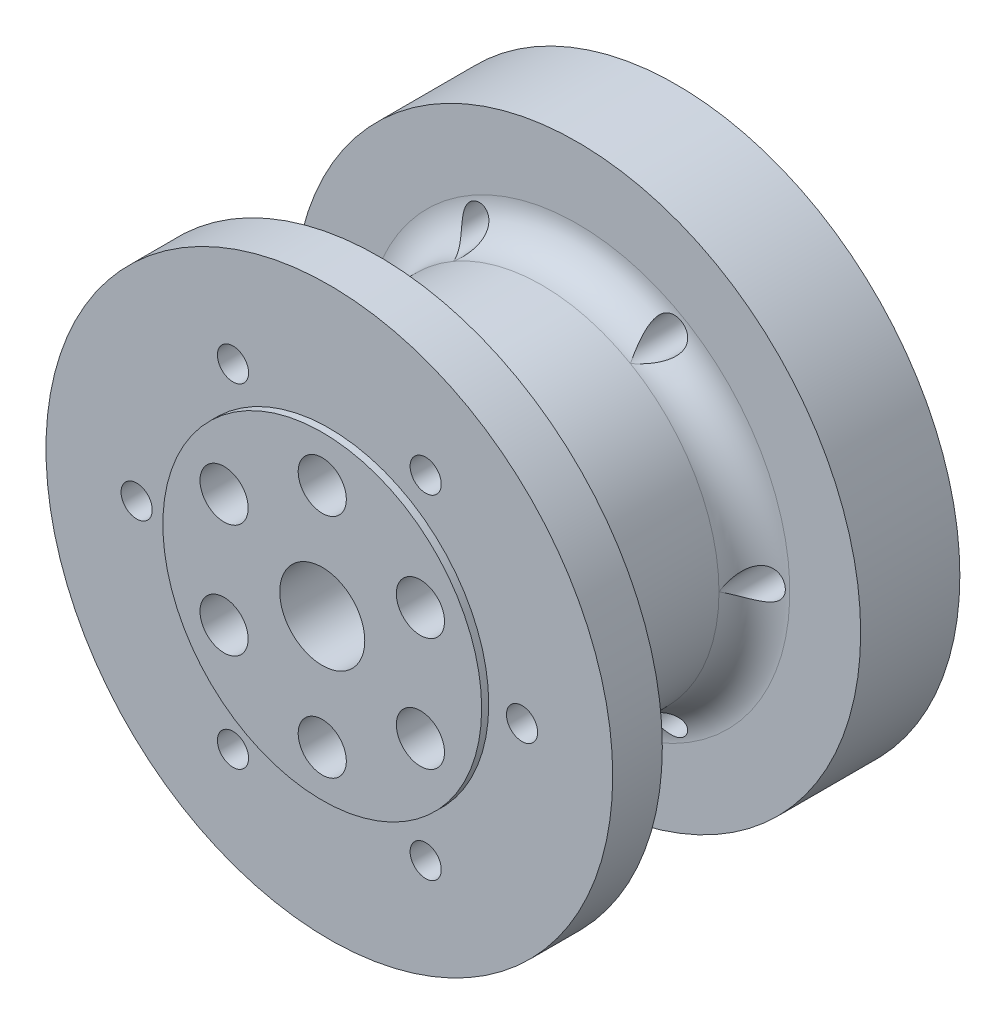
SolidWorks part; units mm, degrees
material "Nylon - impressão"
ref_plane "Plano frontal" through (0, 0, 0) normal (0, 0, 1) x (1, 0, 0)
ref_plane "Plano superior" through (0, 0, 0) normal (0, 1, 0) x (1, 0, 0)
ref_plane "Plano direito" through (0, 0, 0) normal (1, 0, 0) x (0, 0, -1)
sketch "Esboço1" plane through (0, 0, 0) normal (1, 0, 0) x (0, 0, -1)
  line L0 (1.5, 11.25) -> (1.5, 20)
  line L1 (1.5, 20) -> (5, 20)
  line L2 (5, 20) -> (5, 12.5)
  line L3 (5, 12.5) -> (19, 12.5)
  line L4 (19, 12.5) -> (19, 20)
  line L5 (19, 20) -> (27, 20)
  line L6 (27, 20) -> (27, 3)
  line L9 (27, 3) -> (0, 3)
  line L10 (0, 3) -> (0, 11.25)
  line L11 (0, 11.25) -> (1.5, 11.25)
  line L12 (0, 0) -> (24.3309, 0) construction
  line L14 (0, 11.25) -> (-3, 11.25) construction
  line L15 (0, 11.25) -> (0, 3) construction
  line L16 (0, 3) -> (-3, 3) construction
  line L17 (-3, 11.25) -> (-3, 3) construction
  dimension "D1" = 25
  dimension "D2" = 6
  dimension "D3" = 14
  dimension "D4" = 22.5
  dimension "D5" = 30
  dimension "D6" = 5
  dimension "D7" = 1.5
  dimension "D8" = 3
  dimension "D9" = 40
revolve "Revolução1" add sketch "Esboço1" angle 360 about L12
sketch "Esboço2" plane through (0, 0, -27) normal (0, 0, -1) x (-1, 0, 0)
  circle A0 centre (0, 0) radius 8 construction
  circle A1 centre (0, 8) radius 1.6
  circle A2 centre (6.9282, 4) radius 1.6
  circle A3 centre (6.9282, -4) radius 1.6
  circle A4 centre (0, -8) radius 1.6
  circle A5 centre (-6.9282, -4) radius 1.6
  circle A6 centre (-6.9282, 4) radius 1.6
  point P17 (0, 0)
  dimension "D1" = 16
  dimension "D2" = 3.2
  dimension "D3" = 6
extrude "Corte-extrusão1" cut sketch "Esboço2" against normal through all
hole_wizard "Rebaixo para SHCS M31" positions "Esboço3" profile "Esboço4" counterbore size "M3" standard "Ansi Metric" end condition through all
sketch "Esboço3" plane through (0, 0, -27) normal (0, 0, -1) x (-1, 0, 0)
  point P0 (0, 8)
  point P3 (-6.9282, 4)
  point P6 (-6.9282, -4)
  point P9 (0, -8)
  point P12 (6.9282, -4)
  point P15 (6.9282, 4)
sketch "Esboço4" plane through (0, 8, -27) normal (1, 0, 0) x (0, 1, 0)
  line L0 (0, 0) -> (0, 27)
  line L1 (0, 27) -> (1.7, 27)
  line L3 (1.7, 27) -> (1.7, 4)
  line L4 (3.25, 4) -> (1.7, 4)
  line L5 (3.25, 4) -> (3.25, 0.025)
  line L6 (3.25, 0.025) -> (3.275, 0)
  line L7 (3.275, 0) -> (0, 0)
  line L8 (-3.25, 0.025) -> (-3.275, 0) construction
  line L11 (0, -6.35) -> (0, 107.95) construction
  dimension "Thru Hole Dia." = 3.4
  dimension "Thru Hole Depth" = 27
  dimension "C'Bore Dia." = 6.5
  dimension "C'Bore Depth" = 4
  dimension "Near C'Sink Dia." = 6.55
  dimension "Near C'Sink Angle" = 90
sketch "Esboço5" plane through (0, 0, -27) normal (0, 0, -1) x (-1, 0, 0)
  circle A0 centre (0, 0) radius 11.275
extrude "Corte-extrusão2" cut sketch "Esboço5" against normal up to surface (4 mm away) up to face at (5.2282, 4, -23)
fillet "Filete1" radius 2.5 2 edges at (12.5, 0, -19) (12.5, 0, -5)
sketch "Esboço6" plane through (0, 0, -27) normal (0, 0, -1) x (-1, 0, 0)
  line L0 (-13.6, 0) -> (0, 0) construction
  circle A0 centre (0, 0) radius 12.5 construction
  circle A1 centre (0, 0) radius 12.5 construction
  circle A2 centre (-13.6, 0) radius 1.1
  circle A3 centre (-6.8, 11.7779) radius 1.1
  circle A4 centre (6.8, 11.7779) radius 1.1
  circle A5 centre (13.6, 0) radius 1.1
  circle A6 centre (6.8, -11.7779) radius 1.1
  circle A7 centre (-6.8, -11.7779) radius 1.1
  point P22 (0, 0)
  dimension "D1" = 2.2
  dimension "D2" = 6
extrude "Corte-extrusão3" cut sketch "Esboço6" against normal through all both and the other way through all
sketch "Esboço7" plane through (0, 0, -27) normal (0, 0, -1) x (-1, 0, 0)
  circle A0 centre (0, 0) radius 16.5
  dimension "D1" = 33
extrude "Corte-extrusão4" cut sketch "Esboço7" against normal up to surface (4 mm away) up to face at (-8.6282, 4, -23)
sketch "Esboço10" plane through (0, 0, -23) normal (0, 0, -1) x (-1, 0, 0)
  circle A0 centre (0, 0) radius 3 construction
  circle A1 centre (0, 0) radius 3
  circle A2 centre (0, 0) radius 5
  circle M7 centre (0, 0) radius 3
  dimension "D1" = 10
extrude "Ressalto-extrusão3" add sketch "Esboço10" along normal offset from surface (7 mm away) 3 contours A2 M7 region at (4.8586, 0, -23) up to face at (-16.5, 0, -27) offset beyond the face yes
sketch "Esboço11" plane through (0, 0, -27) normal (0, 0, -1) x (-1, 0, 0)
  circle A0 centre (0, 0) radius 16.5 construction
  circle A1 centre (0, 0) radius 20
  circle A2 centre (0, 0) radius 20
  circle A3 centre (0, 0) radius 16.5
  dimension "D1" = 0
extrude "Corte-extrusão6" cut sketch "Esboço11" against normal blind 1
sketch "Esboço12" plane through (0, 0, 0) normal (0, 0, 1) x (1, 0, 0)
  circle A1 centre (0, 0) radius 11.25
  circle A2 centre (0, 0) radius 11.25
  dimension "D1" = 0
extrude "Corte-extrusão7" cut sketch "Esboço12" against normal blind 1
